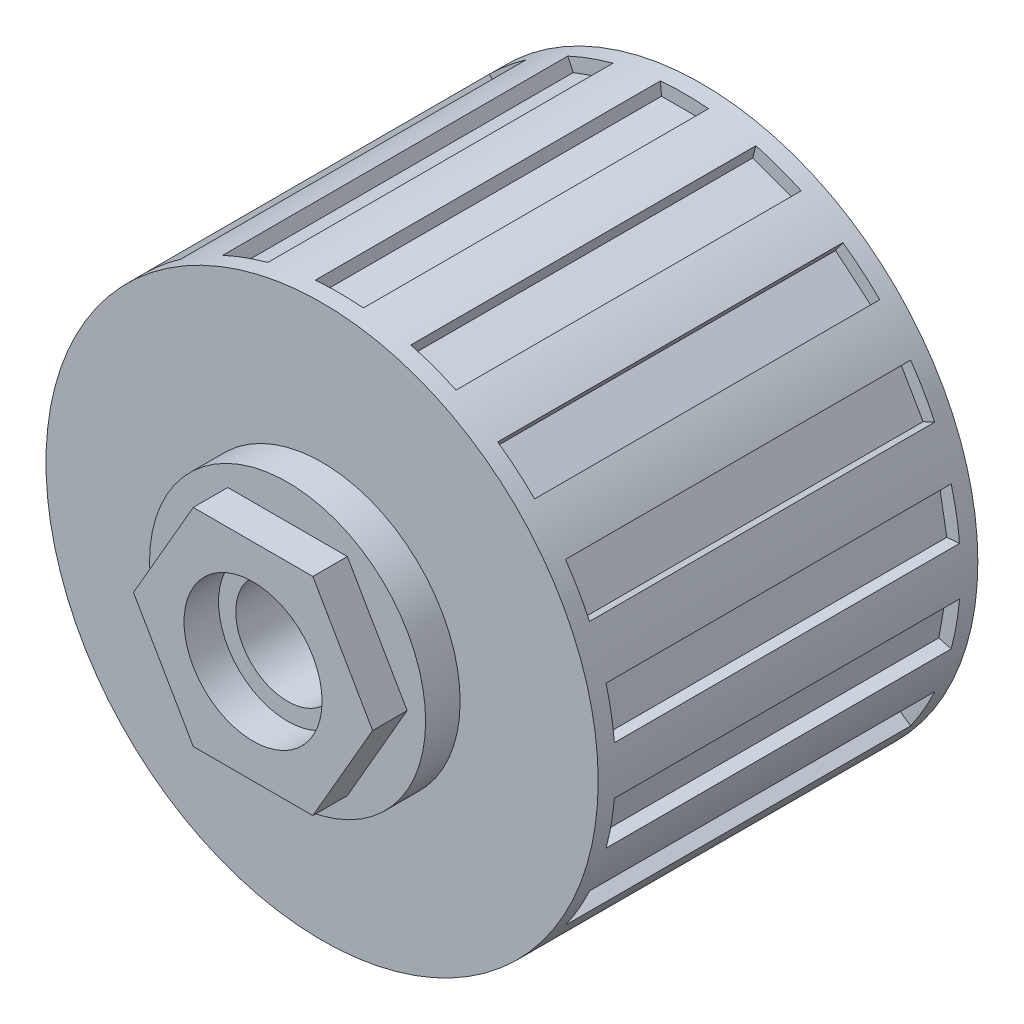
SolidWorks part; units mm, degrees
ref_plane "前视基准面" through (0, 0, 0) normal (0, 0, 1) x (1, 0, 0)
ref_plane "上视基准面" through (0, 0, 0) normal (0, 1, 0) x (1, 0, 0)
ref_plane "右视基准面" through (0, 0, 0) normal (1, 0, 0) x (0, 0, -1)
sketch "草图1" plane through (0, 0, 0) normal (0, 0, 1) x (1, 0, 0)
  circle A0 centre (0, 0) radius 80
  circle A1 centre (0, 0) radius 15
  dimension "D1" = 160
  dimension "D2" = 30
extrude "凸台-拉伸1" add sketch "草图1" along normal blind 120
ref_plane "基准面1" through (0, 0, 105) normal (0, 0, 1) x (1, 0, 0)
sketch "草图2" plane through (0, 0, 105) normal (0, 0, 1) x (1, 0, 0)
  line L0 (-6.6491, 76) -> (-6.9725, 79.6956)
  line L1 (6.6491, 76) -> (6.9725, 79.6956)
  line L2 (0, 80) -> (0, 76) construction
  line L3 (-6.6491, 76) -> (6.6491, 76)
  circle A0 centre (0, 0) radius 80 construction
  arc A1 (6.9725, 79.6956) -> (-6.9725, 79.6956) centre (0, 0) ccw
  dimension "D1" = 5
  dimension "D2" = 5
  dimension "D3" = 4
extrude "切除-拉伸1" cut sketch "草图2" against normal blind 100
pattern_circular "阵列(圆周)1" count 18 over 360 about axis through (0, 0, 120) along (0, 0, -1) of "切除-拉伸1"
sketch "草图3" plane through (0, 0, 120) normal (0, 0, 1) x (1, 0, 0)
  circle A0 centre (0, 0) radius 50
  circle A1 centre (0, 0) radius 20
  dimension "D1" = 40
extrude "凸台-拉伸2" add sketch "草图3" against normal blind 3
sketch "草图4" plane through (0, 0, 120) normal (0, 0, 1) x (1, 0, 0)
  line L1 (34.641, 0) -> (17.3205, 30)
  line L2 (17.3205, 30) -> (-17.3205, 30)
  line L3 (-17.3205, 30) -> (-34.641, 0)
  line L4 (-34.641, 0) -> (-17.3205, -30)
  line L5 (-17.3205, -30) -> (17.3205, -30)
  line L6 (17.3205, -30) -> (34.641, 0)
  circle A0 centre (0, 0) radius 30 construction
  circle A1 centre (0, 0) radius 20
  dimension "D1" = 60
extrude "凸台-拉伸3" add sketch "草图4" along normal blind 10
sketch "草图5" plane through (0, 0, 120) normal (0, 0, 1) x (1, 0, 0)
  circle A0 centre (0, 0) radius 40
  dimension "D1" = 80
extrude "切除-拉伸2" cut sketch "草图5" against normal blind 10 flip side to cut
